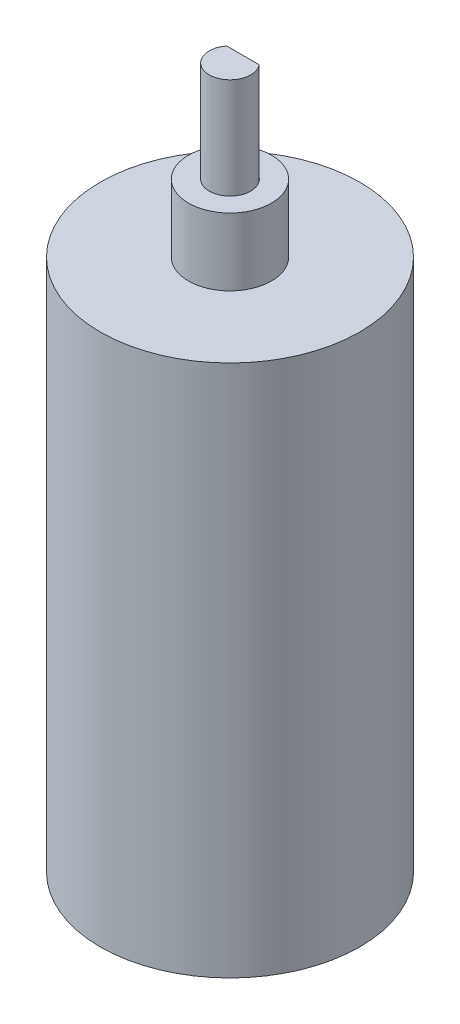
SolidWorks part; units mm, degrees
ref_plane "Front Plane" through (0, 0, 0) normal (0, 0, 1) x (1, 0, 0)
ref_plane "Top Plane" through (0, 0, 0) normal (0, 1, 0) x (1, 0, 0)
ref_plane "Right Plane" through (0, 0, 0) normal (1, 0, 0) x (0, 0, -1)
sketch "Sketch1" plane through (0, 0, 0) normal (0, 1, 0) x (1, 0, 0)
  circle A0 centre (0, 0) radius 12.5
  dimension "D1" = 25
extrude "Boss-Extrude1" add sketch "Sketch1" along normal mid plane 51.3
sketch "Sketch2" plane through (0, 25.65, 0) normal (0, 1, 0) x (1, 0, 0)
  line L0 (-1.5612, 1.25) -> (1.5612, 1.25)
  circle A0 centre (0, 0) radius 2
  circle A1 centre (0, 0) radius 4
  dimension "D1" = 4
  dimension "D3" = 8
  dimension "D2" = 1.25
extrude "Boss-Extrude2" add sketch "Sketch2" along normal blind 16.2 contours L0 A0 | A0 region at (0, 25.65, 0.232)
extrude "Boss-Extrude3" add sketch "Sketch2<3>" along normal blind 6.5 contours A1 A0 region at (-3.8869, 25.65, 0)
sketch "Sketch2<3>" plane through (0, 25.65, 0) normal (0, 1, 0) x (1, 0, 0) same geometry as "Sketch2"
extrude "Cut-Extrude2" cut sketch "Sketch2<4>" along normal offset from surface (17 mm away) 10.5 contours L0 A0 region at (0, 25.65, -1.5554) up to face at (0, 32.15, 2) offset beyond the face yes
sketch "Sketch2<4>" plane through (0, 25.65, 0) normal (0, 1, 0) x (1, 0, 0) same geometry as "Sketch2"
